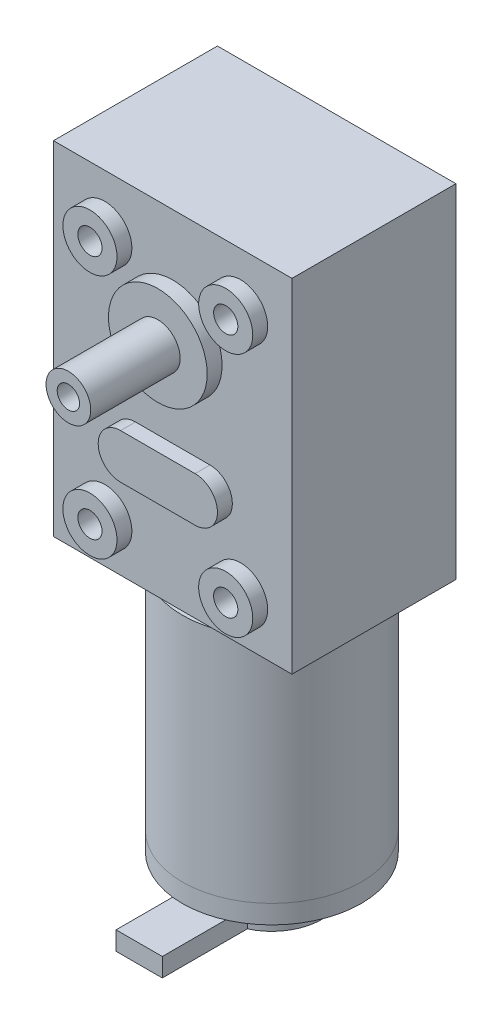
SolidWorks part; units mm, degrees
note: The reader was unsure of these and kept them because the rebuilt part matched: shared geometry of "Sketch1<3>", "Sketch1<4>", "Sketch1<5>", "Sketch1<6>", "Sketch1<7>", "Sketch5<4>".
ref_plane "Front Plane" through (0, 0, 0) normal (0, 0, 1) x (1, 0, 0)
ref_plane "Top Plane" through (0, 0, 0) normal (0, 1, 0) x (1, 0, 0)
ref_plane "Right Plane" through (0, 0, 0) normal (1, 0, 0) x (0, 0, -1)
sketch "Sketch1" plane through (0, 0, 0) normal (0, 0, 1) x (1, 0, 0)
  line L0 (0, 0) -> (0, 23) construction
  line L1 (-16, -23) -> (16, -23)
  line L2 (-16, -23) -> (-16, 23)
  line L3 (-16, 23) -> (16, 23)
  line L4 (16, -23) -> (16, 23)
  line L5 (-16, -23) -> (16, 23) construction
  line L6 (-16, 23) -> (16, -23) construction
  line L7 (-5, -7.1875) -> (5, -7.1875) construction
  line L8 (-5, -4.1875) -> (5, -4.1875)
  line L9 (-5, -10.1875) -> (5, -10.1875)
  circle A1 centre (9.11, 15.77) radius 3.63
  circle A2 centre (9.11, 15.77) radius 1.625
  circle A3 centre (9.11, -17.13) radius 3.63
  circle A4 centre (9.11, -17.13) radius 1.625
  circle A5 centre (-9.11, -17.13) radius 1.625
  circle A6 centre (-9.11, -17.13) radius 3.63
  circle A7 centre (-9.11, 15.77) radius 3.63
  circle A8 centre (-9.11, 15.77) radius 1.625
  arc A9 (-5, -4.1875) -> (-5, -10.1875) centre (-5, -7.1875) ccw
  arc A10 (5, -10.1875) -> (5, -4.1875) centre (5, -7.1875) ccw
  circle A11 centre (0, 8.2) radius 6.62
  circle A12 centre (0, 8.2) radius 3
  circle A13 centre (0, 8.2) radius 1.5
  point P0 (0, 0)
  point P22 (0, -7.1875)
  dimension "D3" = 7.26
  dimension "D4" = 3.25
  dimension "D8" = 7.26
  dimension "D9" = 3.25
  dimension "D10" = 16
  dimension "D12" = 13.24
  dimension "D14" = 6
  dimension "D15" = 3
  dimension "D1" = 46
  dimension "D2" = 32
  dimension "D5" = 6.89
  dimension "D6" = 7.23
  dimension "D7" = 32.9
  dimension "D11" = 6
  dimension "D13" = 14.8
extrude "Boss-Extrude1" add sketch "Sketch1" against normal blind 22 contours L9 A10 L8 A9 | A6 A5 | A1 A2 | A3 A4 | A7 A8 | A8 | A11 A12 | L2 L1 L4 L3
extrude "Boss-Extrude2" add sketch "Sketch1<3>" along normal blind 2 and the other way blind 22 contours A7 A8 | A1 A2 | A3 A4 | A6 A5 | L9 A10 L8 A9
sketch "Sketch1<3>" plane through (0, 0, 0) normal (0, 0, 1) x (1, 0, 0) same geometry as "Sketch1"
extrude "Boss-Extrude3" add sketch "Sketch1<4>" along normal blind 14 contours A12
sketch "Sketch1<4>" plane through (0, 0, 0) normal (0, 0, 1) x (1, 0, 0) same geometry as "Sketch1"
extrude "Boss-Extrude4" add sketch "Sketch1<5>" along normal blind 2 contours A11 A12
sketch "Sketch1<5>" plane through (0, 0, 0) normal (0, 0, 1) x (1, 0, 0) same geometry as "Sketch1"
extrude "Cut-Extrude1" cut sketch "Sketch1<6>" against normal blind 12 contours A8 | A13 | A5 | A4 | A2
sketch "Sketch1<6>" plane through (0, 0, 0) normal (0, 0, 1) x (1, 0, 0) same geometry as "Sketch1"
extrude "Cut-Extrude2" cut sketch "Sketch1<7>" against normal blind 12 and the other way blind 12 contours A2
sketch "Sketch1<7>" plane through (0, 0, 0) normal (0, 0, 1) x (1, 0, 0) same geometry as "Sketch1"
sketch "Sketch2" plane through (0, -23, 0) normal (0, -1, 0) x (1, 0, 0)
  line L3 (1.8, -11.5) -> (1.8, 0) construction
  line L4 (-16, 0) -> (16, 0) construction
  line L5 (-16, -22) -> (16, -22) construction
  circle A0 centre (1.8, -11.5) radius 12
  dimension "D1" = 24
  dimension "D2" = 1.8
  dimension "D3" = 1.5
extrude "Boss-Extrude5" add sketch "Sketch2" along normal blind 31 separate body
sketch "Sketch3" plane through (0, -54, 0) normal (0, -1, 0) x (1, 0, 0)
  circle A0 centre (1.8, -11.5) radius 12
  dimension "D1" = 24
extrude "Boss-Extrude6" add sketch "Sketch3" along normal blind 2.5 separate body
sketch "Sketch4" plane through (0, -56.5, 0) normal (0, -1, 0) x (1, 0, 0)
  circle A0 centre (1.8, -11.5) radius 6.7
  dimension "D1" = 13.4
extrude "Boss-Extrude7" add sketch "Sketch4" along normal blind 4.5 separate body
sketch "Sketch5" plane through (0, 0, 0) normal (0, 0, 1) x (1, 0, 0)
  line L0 (-4.9, -61) -> (8.5, -61) construction
  line L1 (-1.6, -61) -> (4.6, -61)
  line L2 (-1.6, -61) -> (-1.6, -58.5)
  line L3 (-1.6, -58.5) -> (4.6, -58.5)
  line L4 (4.6, -61) -> (4.6, -58.5)
  line L5 (-4.9, -56.5) -> (-4.9, -61) construction
  line L6 (-0.4, -58.5) -> (-0.4, -61)
  line L7 (0.8, -58.5) -> (0.8, -61)
  line L8 (1.8, -58.5) -> (1.8, -61)
  line L9 (1.8, -61) -> (1.8, -56.5) construction
  line L10 (3, -58.5) -> (3, -61)
  dimension "D1" = 2.5
  dimension "D2" = 6.2
  dimension "D3" = 3.3
  dimension "D4" = 1.2
  dimension "D5" = 1.2
  dimension "D6" = 1.2
extrude "Cut-Extrude4" cut sketch "Sketch5" against normal blind 6 contours L3 L10 L1 L4 | L10 L3 L8 L1 | L8 L3 L7 L1 | L7 L3 L6 L1 | L6 L3 L2 L1
extrude "Boss-Extrude9" add sketch "Sketch5<4>" along normal blind 6 and the other way blind 6 separate body contours L6 L3 L2 L1 | L7 L3 L6 L1 | L8 L3 L7 L1 | L10 L3 L8 L1 | L3 L10 L1 L4
sketch "Sketch5<4>" plane through (0, 0, 0) normal (0, 0, 1) x (1, 0, 0) same geometry as "Sketch5"
sketch "Sketch6" plane through (0, 0, 14) normal (0, 0, 1) x (1, 0, 0)
  circle A0 centre (0, 8.2) radius 3
sketch "Sketch7" plane through (0, 0, 14) normal (0, 0, 1) x (1, 0, 0)
  line L0 (52.5, 8.2) -> (65, 8.2)
  line L1 (65, 8.2) -> (52.5, 8.2)
  circle A0 centre (0, 8.2) radius 65
  dimension "D1" = 130
  dimension "D2" = 12.5
